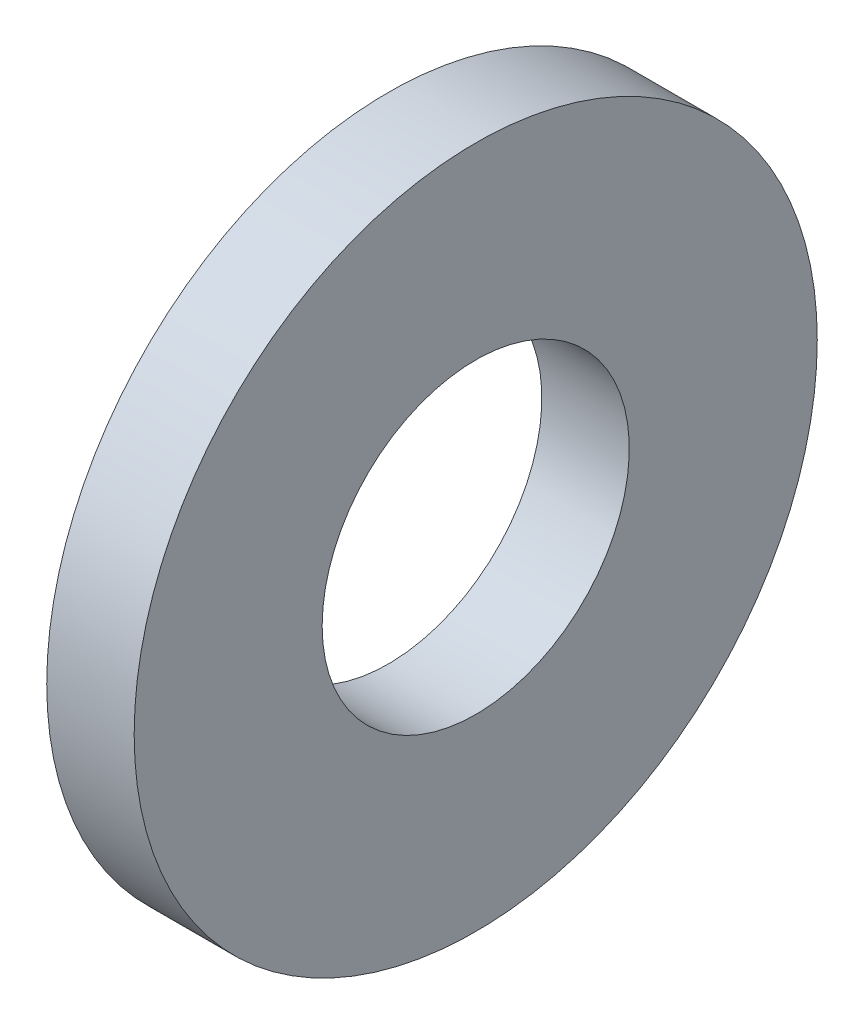
SolidWorks part; units mm, degrees
material "Plain Carbon Steel"
ref_plane "Front Plane" through (0, 0, 0) normal (0, 0, 1) x (1, 0, 0)
ref_plane "Top Plane" through (0, 0, 0) normal (0, 1, 0) x (1, 0, 0)
ref_plane "Right Plane" through (0, 0, 0) normal (1, 0, 0) x (0, 0, -1)
sketch "Sketch1" plane through (0, 0, 0) normal (1, 0, 0) x (0, 0, -1)
  circle A0 centre (0, 0) radius 7.9375
  circle A1 centre (0, 0) radius 3.5687
  dimension "OD" = 15.875
  dimension "ID" = 7.1374
extrude "Boss-Extrude1" add sketch "Sketch1" along normal blind 2.032
